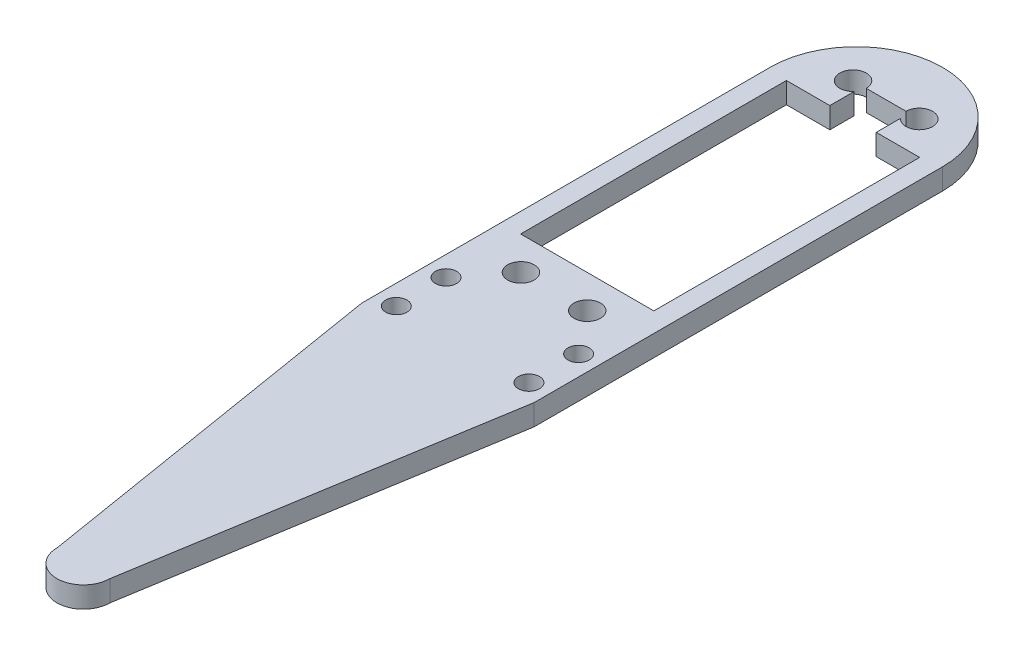
SolidWorks part; units mm, degrees
ref_plane "Front Plane" through (0, 0, 0) normal (0, 0, 1) x (1, 0, 0)
ref_plane "Top Plane" through (0, 0, 0) normal (0, 1, 0) x (1, 0, 0)
ref_plane "Right Plane" through (0, 0, 0) normal (1, 0, 0) x (0, 0, -1)
sketch "Sketch2" plane through (0, 0, 0) normal (0, 1, 0) x (1, 0, 0)
  line L0 (-13, 0) -> (-13, -61.6)
  line L1 (13, 0) -> (13, -61.6)
  line L2 (-13, -61.6) -> (-4, -116.6)
  line L3 (13, -61.6) -> (4, -116.6)
  line L4 (0, 13) -> (0, -120.6) construction
  line L5 (-4, -116.6) -> (4, -116.6) construction
  line L6 (-10.05, -0.5) -> (10.05, -0.5)
  line L7 (-10.05, -0.5) -> (-10.05, -40.6)
  line L8 (-10.05, -40.6) -> (10.05, -40.6)
  line L9 (10.05, -0.5) -> (10.05, -40.6)
  line L10 (-10.05, -0.5) -> (10.05, -40.6) construction
  line L11 (-10.05, -40.6) -> (10.05, -0.5) construction
  arc A0 (13, 0) -> (-13, 0) centre (0, 0) ccw
  arc A1 (-4, -116.6) -> (4, -116.6) centre (0, -116.6) ccw
  circle A2 centre (-5, 4.5) radius 2
  circle A4 centre (-5, -45.6) radius 2
  circle A5 centre (5, -45.6) radius 2
  circle A6 centre (5, 4.5) radius 2
  point P15 (0, -20.55)
  dimension "D1" = 4
  dimension "D8" = 13
  dimension "D10" = 4
  dimension "D2" = 50.1
  dimension "D3" = 5
  dimension "D4" = 4.5
  dimension "D5" = 40.1
  dimension "D6" = 20.1
  dimension "D7" = 5
  dimension "D9" = 55
  dimension "D11" = 16
extrude "Boss-Extrude1" add sketch "Sketch2" along normal blind 3.175
sketch "Sketch3" plane through (0, 3.175, 0) normal (0, 1, 0) x (1, 0, 0)
  circle A0 centre (10, -59.4) radius 1.6 construction
  circle A1 centre (10, -51.9) radius 1.6 construction
  circle A2 centre (-10, -59.4) radius 1.6 construction
  circle A3 centre (-10, -51.9) radius 1.6 construction
  circle A4 centre (10, -59.4) radius 1.6
  circle A5 centre (10, -51.9) radius 1.6
  circle A6 centre (-10, -59.4) radius 1.6
  circle A7 centre (-10, -51.9) radius 1.6
extrude "Cut-Extrude1" cut sketch "Sketch3" against normal through all both and the other way through all
sketch "Sketch4" plane through (0, 3.175, 0) normal (0, 1, 0) x (1, 0, 0)
  line L0 (10.05, -0.5) -> (-10.05, -0.5) construction
  line L1 (-3.5, 4.5) -> (3.5, 4.5)
  line L2 (-3.5, 4.5) -> (-3.5, -0.5)
  line L3 (-3.5, -0.5) -> (3.5, -0.5)
  line L4 (3.5, 4.5) -> (3.5, -0.5)
  line L5 (-3.5, 4.5) -> (3.5, -0.5) construction
  line L6 (-3.5, -0.5) -> (3.5, 4.5) construction
  point P0 (0, 2)
  point P5 (0, -0.5)
  point P6 (0, 0)
  dimension "D1" = 7
  dimension "D2" = 5
extrude "Cut-Extrude2" cut sketch "Sketch4" along direction (0, 1, 0) on the side against the normal up to surface (3.175 mm away) up to face at (10, 0, 53.5)
